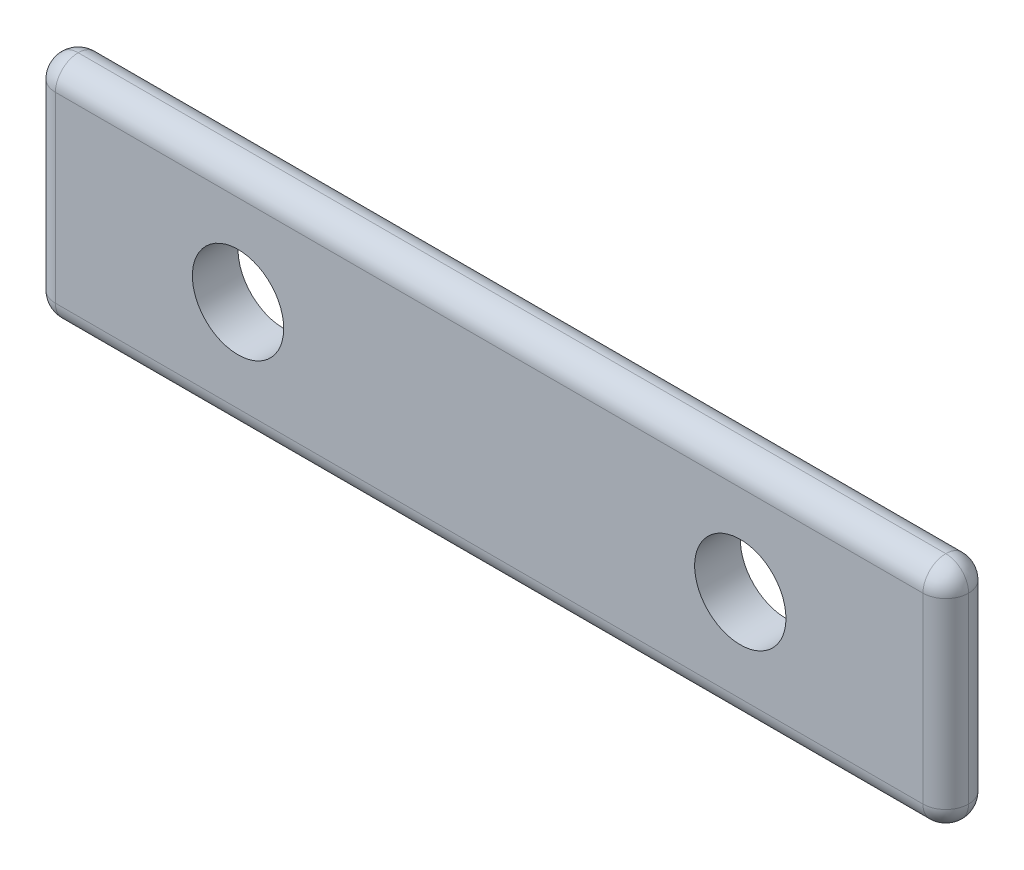
SolidWorks part; units mm, degrees
ref_plane "Plano frontal" through (0, 0, 0) normal (0, 0, 1) x (1, 0, 0)
ref_plane "Plano superior" through (0, 0, 0) normal (0, 1, 0) x (1, 0, 0)
ref_plane "Plano direito" through (0, 0, 0) normal (1, 0, 0) x (0, 0, -1)
sketch "Esboço1" plane through (0, 0, 0) normal (0, 0, 1) x (1, 0, 0)
  line L4 (0, 0) -> (0, 50)
  line L5 (0, 50) -> (200, 50)
  line L6 (200, 50) -> (200, 0)
  line L7 (200, 0) -> (0, 0)
  point P2 (200, 0)
  dimension "D1" = 200
  dimension "D2" = 50
extrude "Ressalto-extrusão1" add sketch "Esboço1" along normal blind 10
fillet "Filete1" radius 5 8 edges at (200, 25, 0) (200, 25, 10) (0, 25, 0) (0, 25, 10) (100, 0, 0) (100, 0, 10) (100, 50, 0) (100, 50, 10)
hole_wizard "Furos-guia com Ø20.0mm1" positions "Esboço7" profile "Esboço8" hole size "Ø20.0" standard "Ansi Metric" end condition through all
sketch "Esboço7" plane through (0, 0, 10) normal (0, 0, 1) x (1, 0, 0)
  line L0 (0, 5) -> (0, 45) construction
  point P0 (45, 25.2069)
  point P2 (155, 25.2069)
  dimension "D1" = 110
  dimension "D2" = 45
sketch "Esboço8" plane through (45, 25.2069, 10) normal (1, 0, 0) x (0, -1, 0)
  line L0 (0, 0) -> (0, 10)
  line L1 (0, 10) -> (10, 10)
  line L2 (10, 10) -> (10, 0)
  line L5 (10, 0) -> (0, 0)
  line L11 (0, -6.35) -> (0, 107.95) construction
  dimension "Thru Hole Dia." = 20
  dimension "Thru Hole Depth" = 10
